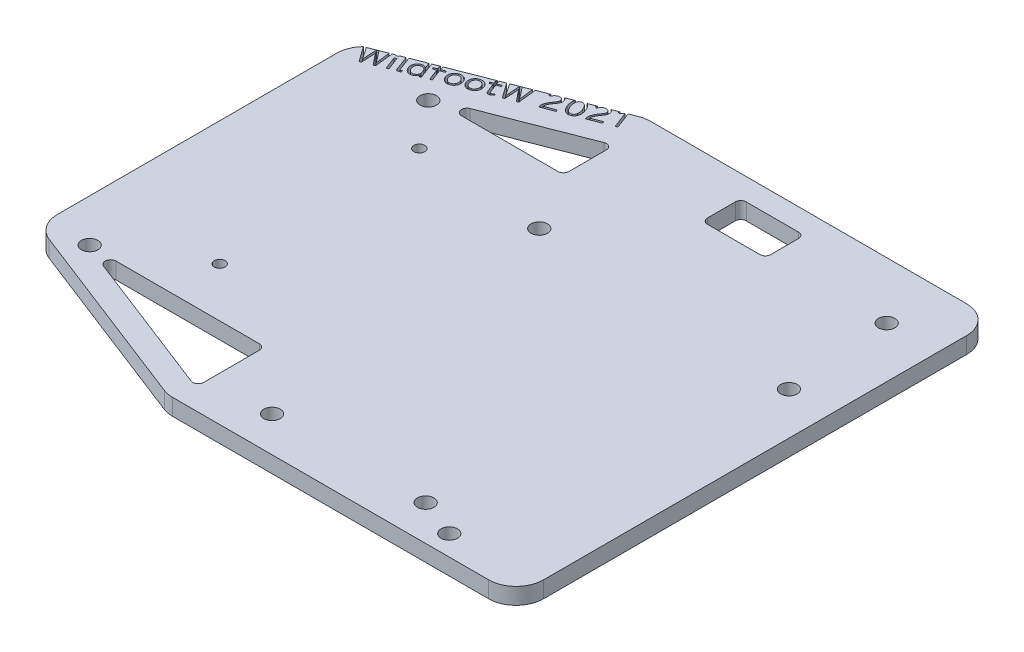
SolidWorks part; units mm, degrees
ref_plane "Front Plane" through (0, 0, 0) normal (0, 0, 1) x (1, 0, 0)
ref_plane "Top Plane" through (0, 0, 0) normal (0, 1, 0) x (1, 0, 0)
ref_plane "Right Plane" through (0, 0, 0) normal (1, 0, 0) x (0, 0, -1)
ref_plane "Plane1" through (0, 33, 0) normal (0, 1, 0) x (1, 0, 0)
sketch "Sketch1" plane through (0, 33, 0) normal (0, 1, 0) x (1, 0, 0)
  line L1 (0.59, -43.5583) -> (102.551, -43.5583)
  line L2 (0.59, -43.5583) -> (0.59, 43.5583)
  line L3 (0.59, 43.5583) -> (102.551, 43.5583)
  line L4 (102.551, -43.5583) -> (102.551, 43.5583)
  line L6 (0.59, 28.6267) -> (38.9977, 43.5583)
  line L8 (0.59, 28.6267) -> (38.9977, 28.6267) construction
  line L9 (38.9977, 28.6267) -> (38.9977, 43.5583) construction
  line L10 (6.0167, 0) -> (0.59, 0) construction
  line L11 (6.0167, 23.2) -> (6.0167, -23.2) construction
  line L12 (38.9977, 28.6267) -> (38.9977, 23.2) construction
  line L13 (40.3167, 23.2) -> (6.0167, 23.2) construction
  line L14 (38.9977, 28.6267) -> (44.4243, 28.6267) construction
  line L15 (44.4243, 28.4878) -> (44.4243, -37.1122) construction
  line L16 (0.59, -28.6267) -> (38.9977, -43.5583)
  line L17 (102.551, 0) -> (97.1243, 0) construction
  line L19 (97.1243, -37.1122) -> (97.1243, 28.4878) construction
  point P6 (0.59, 0)
extrude "Boss-Extrude1" add sketch "Sketch1" along normal blind 3 contours L2 L1 L4 L3 region at (54.2056, 33, 0)
sketch "Sketch2" plane through (0, 33, 0) normal (0, -1, 0) x (1, 0, 0)
  line L1 (3.0097, -26.2413) -> (36.7372, -39.3535) construction
  line L2 (0.59, -28.6267) -> (38.9977, -43.5583) construction
  text T0 "WildfootW 2021" font "@BIZ UDPGothic" height 3.5
  dimension "D1" = 3.1
extrude "Cut-Extrude1" cut sketch "Sketch2" against normal up to surface (3 mm away) up to face at (47.3796, 36, 0)
sketch "Sketch3" plane through (0, 33, 0) normal (0, 1, 0) x (1, 0, 0)
  line L0 (16.5148, 27.2) -> (40.4243, 36.4952)
  line L1 (40.4243, 36.4952) -> (40.4243, 27.2)
  line L2 (40.4243, 27.2) -> (16.5148, 27.2)
  line L3 (3.0097, 26.2413) -> (36.7372, 39.3535) construction
  line L4 (7.9594, -27.2) -> (40.4243, -27.2)
  line L5 (40.4243, -27.2) -> (40.4243, -39.8213)
  line L6 (40.4243, -39.8213) -> (7.9594, -27.2)
  line L7 (0.59, -28.6267) -> (38.9977, -43.5583) construction
  line L8 (40.4243, -27.2) -> (40.4243, -23.2) construction
  line L9 (44.4243, 28.4878) -> (44.4243, -37.1122) construction
  line L10 (44.4243, -27.2) -> (40.4243, -27.2) construction
  line L11 (6.0167, -23.2) -> (40.3167, -23.2) construction
  line L12 (24.1919, -33.5106) -> (22.7425, -37.2388) construction
  line L13 (40.4243, 27.2) -> (40.4243, 23.2) construction
  line L14 (40.3167, 23.2) -> (6.0167, 23.2) construction
  line L15 (40.4243, 27.2) -> (44.4243, 27.2) construction
  line L16 (28.4696, 31.8476) -> (27.0202, 35.5758) construction
  line L17 (56.4243, 31.8878) -> (60.3791, 32.4878) construction
  line L18 (60.3791, 32.4878) -> (71.9243, 32.4878)
  line L19 (60.3791, 32.4878) -> (60.3791, 39.5583)
  line L20 (60.3791, 39.5583) -> (71.9243, 39.5583)
  line L21 (71.9243, 32.4878) -> (71.9243, 39.5583)
  line L22 (60.3791, 32.4878) -> (60.3791, 28.4878) construction
  line L23 (75.9243, 28.4878) -> (56.4243, 28.4878) construction
  line L24 (71.9243, 32.4878) -> (75.9243, 32.4878) construction
  line L25 (75.9243, 35.7878) -> (75.9243, 19.1878) construction
  line L26 (71.9243, 39.5583) -> (71.9243, 43.5583) construction
  line L27 (38.9977, 43.5583) -> (102.551, 43.5583) construction
  dimension "D1" = 4
extrude "Cut-Extrude2" cut sketch "Sketch3" along normal up to surface (3 mm away) up to face at (22.3045, 36, -33.601)
fillet "Fillet1" radius 5 6 edges at (102.551, 34.5, 43.5583) (38.9977, 34.5, 43.5583) (0.59, 34.5, 28.6267) (0.59, 34.5, -28.6267) (38.9977, 34.5, -43.5583) (102.551, 34.5, -43.5583)
fillet "Fillet2" radius 1 10 edges at (60.3791, 34.5, -39.5583) (71.9243, 34.5, -39.5583) (40.4243, 34.5, -36.4952) (16.5148, 34.5, -27.2) (60.3791, 34.5, -32.4878) (71.9243, 34.5, -32.4878) (40.4243, 34.5, -27.2) (40.4243, 34.5, 39.8213) (40.4243, 34.5, 27.2) (7.9594, 34.5, 27.2)
sketch "Sketch4" plane through (0, 33, 0) normal (0, 1, 0) x (1, 0, 0)
  circle A0 centre (8.3674, -27.0854) radius 1.5
  circle A1 centre (86.6598, -39.8422) radius 1.5
  circle A2 centre (93.3054, 33.2195) radius 1.5
  circle A3 centre (16.3794, 26.6064) radius 1.5
  circle A4 centre (16.3794, 26.6064) radius 1.5 construction
  circle A5 centre (93.3054, 33.2195) radius 1.5 construction
  circle A6 centre (86.6598, -39.8422) radius 1.5 construction
  circle A7 centre (8.3674, -27.0854) radius 1.5 construction
  circle A8 centre (23.1667, -18.2) radius 1
  circle A9 centre (23.1667, 18.2) radius 1
  circle A10 centre (94.8243, 13.8878) radius 1.5
  circle A11 centre (46.7243, 16.4878) radius 1.5
  circle A12 centre (51.6243, -37.1122) radius 1.5
  circle A13 centre (79.6243, -37.1122) radius 1.5
  circle A14 centre (79.6243, -37.1122) radius 1.5 construction
  circle A15 centre (51.6243, -37.1122) radius 1.5 construction
  circle A16 centre (23.1667, -18.2) radius 1 construction
  circle A17 centre (23.1667, 18.2) radius 1 construction
  arc A18 (47.4243, 17.8144) -> (47.6243, 17.6878) centre (46.7243, 16.4878) ccw construction
  circle A19 centre (94.8243, 13.8878) radius 1.5 construction
extrude "Cut-Extrude3" cut sketch "Sketch4" along normal up to surface (3 mm away) up to face at (23.4446, 36, -32.2467)
